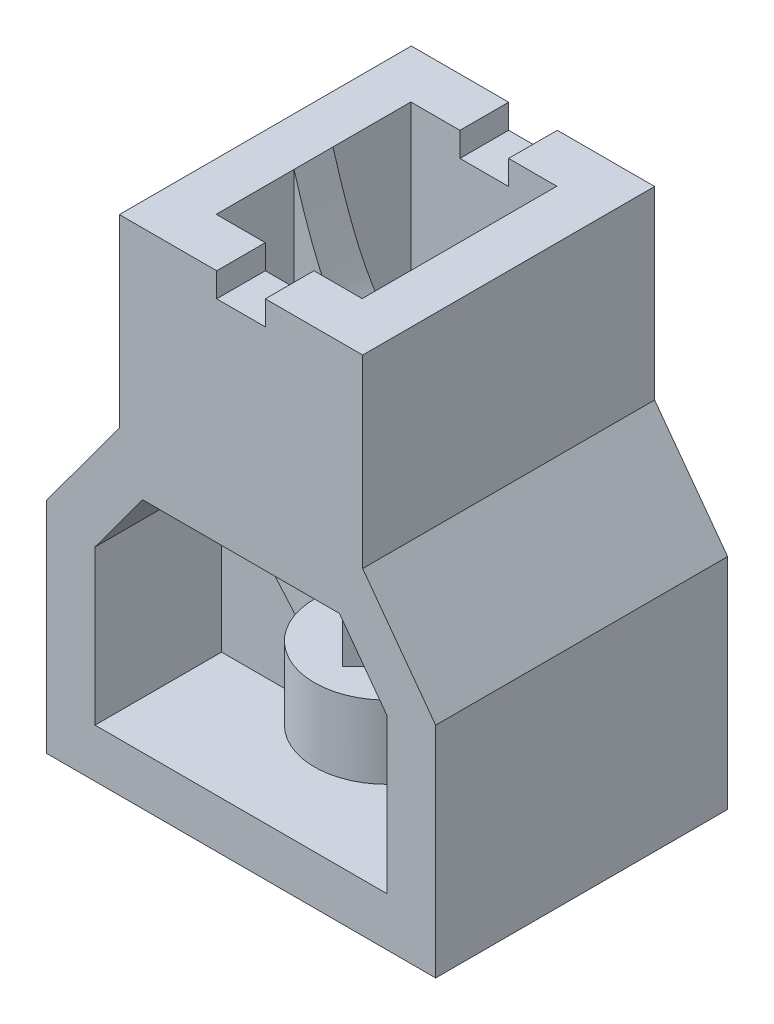
SolidWorks part; units mm, degrees
ref_plane "Спереди" through (0, 0, 0) normal (0, 0, 1) x (1, 0, 0)
ref_plane "Сверху" through (0, 0, 0) normal (0, 1, 0) x (1, 0, 0)
ref_plane "Справа" through (0, 0, 0) normal (1, 0, 0) x (0, 0, -1)
other "Configuration Table"
sketch "Эскиз1" plane through (0, 0, 0) normal (0, 0, 1) x (1, 0, 0)
  line L0 (0, 0) -> (80, 0)
  line L1 (80, 0) -> (80, 45)
  line L2 (0, 0) -> (0, 45)
  line L3 (40, -17.5596) -> (40, 103.3711) construction
  line L4 (65, 65.3711) -> (80, 45)
  line L5 (40, 103.3711) -> (65, 103.3711)
  line L6 (40, 103.3711) -> (15, 103.3711)
  line L7 (65, 103.3711) -> (65, 65.3711)
  line L8 (15, 103.3711) -> (15, 65.3711)
  line L9 (15, 65.3711) -> (0, 45)
  line L10 (10, 10) -> (70, 10)
  line L16 (10, 41.7155) -> (19.7819, 55)
  line L17 (10, 10) -> (10, 41.7155)
  line L18 (70, 41.7155) -> (70, 10)
  line L19 (70, 41.7155) -> (60.2181, 55)
  line L20 (19.7819, 55) -> (60.2181, 55)
  dimension "D1" = 80
  dimension "D2" = 45
  dimension "D3" = 45
  dimension "D4" = 10
  dimension "D5" = 25
  dimension "D6" = 25
  dimension "D7" = 38
  dimension "D8" = 60
  dimension "D9" = 10
  dimension "D10" = 10
  dimension "D11" = 45
  dimension "D12" = 10
extrude "Бобышка-Вытянуть1" add sketch "Эскиз1" along normal blind 30 and the other way blind 30
sketch "Эскиз2" plane through (0, 103.3711, 0) normal (0, 1, 0) x (1, 0, 0)
  line L1 (24.907, -20.0065) -> (54.907, -20.0065)
  line L2 (24.907, -20.0065) -> (24.907, 19.9935)
  line L3 (24.907, 19.9935) -> (54.907, 19.9935)
  line L4 (54.907, -20.0065) -> (54.907, 19.9935)
  line L5 (24.907, -20.0065) -> (54.907, 19.9935) construction
  line L6 (24.907, 19.9935) -> (54.907, -20.0065) construction
  point P0 (39.907, -0.0065)
  dimension "D1" = 30
  dimension "D2" = 40
extrude "Вырез-Вытянуть1" cut sketch "Эскиз2" against normal blind 32
sketch "Эскиз3" plane through (0, 0, 30) normal (0, 0, 1) x (1, 0, 0)
  line L0 (65, 103.3711) -> (15, 103.3711) construction
  line L1 (35, 108.3711) -> (45, 108.3711)
  line L2 (35, 108.3711) -> (35, 98.3711)
  line L3 (35, 98.3711) -> (45, 98.3711)
  line L4 (45, 108.3711) -> (45, 98.3711)
  line L5 (35, 108.3711) -> (45, 98.3711) construction
  line L6 (35, 98.3711) -> (45, 108.3711) construction
  point P0 (40, 103.3711)
  dimension "D1" = 10
  dimension "D2" = 5
extrude "Вырез-Вытянуть2" cut sketch "Эскиз3" against normal through all
sketch "Эскиз4" plane through (0, 10, 0) normal (0, 1, 0) x (1, 0, 0)
  circle A0 centre (40, 0) radius 14.907
extrude "Бобышка-Вытянуть2" add sketch "Эскиз4" along normal blind 15
sketch "Эскиз5" plane through (0, 25, 0) normal (0, 1, 0) x (1, 0, 0)
  line L1 (40, 9.1924) -> (30.8076, 0)
  line L2 (30.8076, 0) -> (40, -9.1924)
  line L3 (40, -9.1924) -> (49.1924, 0)
  line L4 (49.1924, 0) -> (40, 9.1924)
  circle A0 centre (40, 0) radius 6.5 construction
  dimension "D1" = 13
extrude "Вырез-Вытянуть3" cut sketch "Эскиз5" against normal through all and the other way blind 37
sketch "Эскиз6" plane through (0, 0, 0) normal (0, 0, 1) x (1, 0, 0)
  line L0 (70, 10) -> (51.5418, 10)
  line L2 (70, 10) -> (70, 41.7155)
  line L3 (70, 41.7155) -> (51.5418, 20.4047)
  line L4 (51.5418, 20.4047) -> (51.5418, 10)
  line L5 (40, 2.7543) -> (40, 54.1761) construction
  line L6 (10, 10) -> (10, 41.7155)
  line L7 (10, 41.7155) -> (28.4582, 20.4047)
  line L8 (28.4582, 20.4047) -> (28.4582, 10)
  line L9 (10, 10) -> (28.4582, 10)
extrude "Бобышка-Вытянуть3" add sketch "Эскиз6" along normal blind 4 and the other way blind 4
sketch "Эскиз8" plane through (0, 0, 0) normal (0, 0, 1) x (1, 0, 0)
  line L0 (54.907, 103.3711) -> (54.907, 77.3711)
  line L1 (54.907, 71.3711) -> (54.907, 103.3711) construction
  line L3 (24.907, 71.3711) -> (24.907, 103.3711) construction
  line L4 (24.907, 77.3711) -> (24.907, 103.3711)
  line L5 (24.907, 77.3711) -> (24.907, 71.3711)
  line L6 (24.907, 71.3711) -> (54.907, 71.3711)
  line L7 (54.907, 71.3711) -> (54.907, 77.3711)
  spline S0 degree 2 poles (24.907, 103.3711) (39.907, 51.3711) (54.907, 103.3711) knots 0 0 0 1 1 1
  dimension "D1" = 26
extrude "Бобышка-Вытянуть4" add sketch "Эскиз8" along normal blind 4 and the other way blind 4
